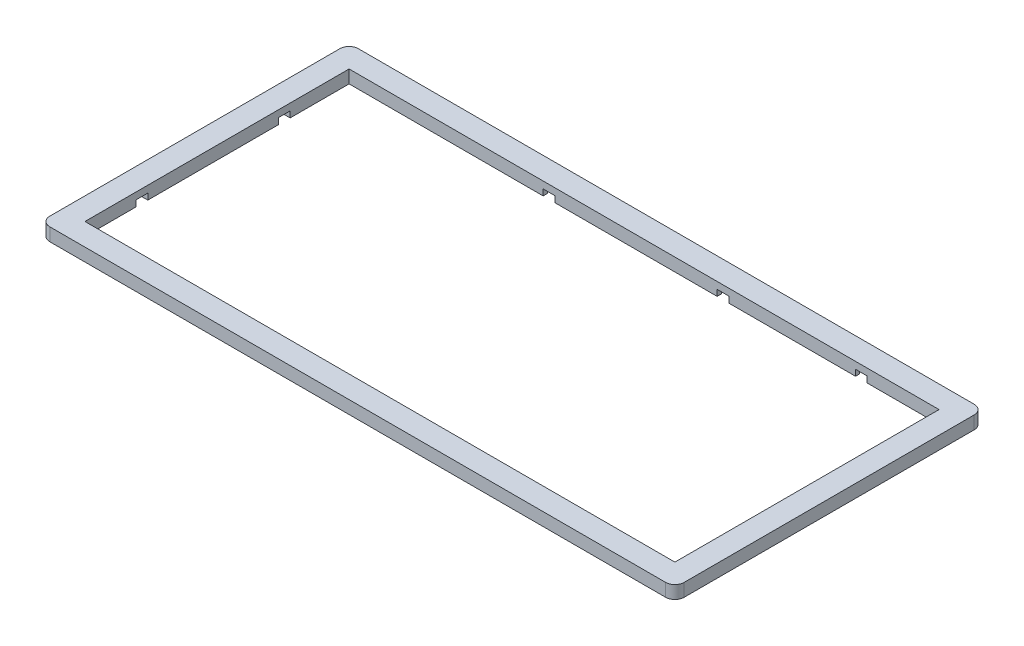
SolidWorks part; units mm, degrees
ref_plane "Front Plane" through (0, 0, 0) normal (0, 0, 1) x (1, 0, 0)
ref_plane "Top Plane" through (0, 0, 0) normal (0, 1, 0) x (1, 0, 0)
ref_plane "Right Plane" through (0, 0, 0) normal (1, 0, 0) x (0, 0, -1)
sketch "Sketch1" plane through (0, 0, 0) normal (0, 1, 0) x (1, 0, 0)
  line L0 (-142.8618, 0) -> (191.3602, 0) construction
  line L1 (0, 90.7825) -> (0, -132.7671) construction
  line L2 (-159.54, 78.7825) -> (159.54, 78.7825)
  line L3 (159.54, 78.7825) -> (159.54, -64.0925)
  line L4 (159.54, -64.0925) -> (-159.54, -64.0925)
  line L5 (-159.54, -64.0925) -> (-159.54, 78.7825)
  line L6 (-171.54, 90.7825) -> (171.54, 90.7825)
  line L7 (171.54, 90.7825) -> (171.54, -76.0925)
  line L8 (171.54, -76.0925) -> (-171.54, -76.0925)
  line L9 (-171.54, -76.0925) -> (-171.54, 90.7825)
  dimension "D1" = 319.08
  dimension "D2" = 142.875
  dimension "D3" = 12
  dimension "D4" = 12
  dimension "D5" = 12
  dimension "D6" = 12
extrude "Boss-Extrude1" add sketch "Sketch1" along normal blind 7
sketch "Sketch3" plane through (0, 0, 0) normal (0, -1, 0) x (1, 0, 0)
  line L0 (-23.85, -81.0825) -> (-48.3, -81.0825)
  line L1 (-23.85, -85.5825) -> (-23.85, -81.0825)
  line L2 (-79.05, -85.5825) -> (-23.85, -85.5825)
  line L3 (-79.05, -81.0825) -> (-79.05, -85.5825)
  line L4 (-54.6, -81.0825) -> (-79.05, -81.0825)
  line L5 (-54.6, -78.7825) -> (-54.6, -81.0825)
  line L6 (-48.3, -78.7825) -> (-54.6, -78.7825)
  line L7 (-48.3, -81.0825) -> (-48.3, -78.7825)
  line L16 (159.54, -78.7825) -> (-159.54, -78.7825) construction
  line L17 (-159.54, -78.7825) -> (-159.54, 64.0925) construction
  line L18 (145.09, -81.0825) -> (120.64, -81.0825)
  line L19 (145.09, -85.5825) -> (145.09, -81.0825)
  line L20 (89.89, -85.5825) -> (145.09, -85.5825)
  line L21 (89.89, -81.0825) -> (89.89, -85.5825)
  line L22 (114.34, -81.0825) -> (89.89, -81.0825)
  line L23 (114.34, -78.7825) -> (114.34, -81.0825)
  line L24 (120.64, -78.7825) -> (114.34, -78.7825)
  line L25 (120.64, -81.0825) -> (120.64, -78.7825)
  line L26 (70.1228, -85.5821) -> (70.1785, -81.0825)
  line L27 (14.9228, -85.5821) -> (70.1228, -85.5821)
  line L28 (14.9785, -81.0825) -> (14.9228, -85.5821)
  line L29 (39.5, -81.0825) -> (14.9785, -81.0825)
  line L30 (39.5, -78.7825) -> (39.5, -81.0825)
  line L31 (45.8, -78.7825) -> (39.5, -78.7825)
  line L32 (45.8, -81.0825) -> (45.8, -78.7825)
  line L33 (70.1785, -81.0825) -> (45.8, -81.0825)
  line L34 (-164.3573, -2.842) -> (-164.3573, -14.017) construction
  line L35 (-159.54, 36.3925) -> (-159.54, 30.0925)
  line L36 (-159.54, 36.3925) -> (-162.84, 36.3925)
  line L37 (-159.54, 30.0925) -> (-162.84, 30.0925)
  line L38 (-162.84, 36.3925) -> (-162.84, 56.3925)
  line L39 (-162.84, 30.0925) -> (-162.84, 10.0925)
  line L40 (-162.84, 56.3925) -> (-167.34, 56.3925)
  line L41 (-167.34, 56.3925) -> (-167.34, 10.0925)
  line L42 (-167.34, 10.0925) -> (-162.84, 10.0925)
  line L43 (-167.3573, -8.4295) -> (-164.3573, -8.4295) construction
  line L44 (-167.3573, 2.6105) -> (-167.3573, -19.4695) construction
  line L45 (-159.54, -40.5825) -> (-159.54, -46.8825)
  line L46 (-159.54, -40.5825) -> (-162.84, -40.5825)
  line L47 (-159.54, -46.8825) -> (-162.84, -46.8825)
  line L48 (-162.84, -40.5825) -> (-162.84, -16.1325)
  line L49 (-162.84, -16.1325) -> (-167.34, -16.1325)
  line L50 (-167.34, -16.1325) -> (-167.34, -71.3325)
  line L51 (-167.34, -71.3325) -> (-162.84, -71.3325)
  line L52 (-162.84, -71.3325) -> (-162.84, -46.8825)
  line L53 (161.84, 10.0925) -> (161.84, 30.0925)
  line L54 (-159.54, 64.0925) -> (159.54, 64.0925) construction
  line L55 (159.54, 64.0925) -> (159.54, -78.7825) construction
  line L56 (151.2867, -7.345) -> (183.3703, -7.345) construction
  line L57 (0, 81.7249) -> (0, 49.7201) construction
  line L58 (159.54, -40.5825) -> (161.84, -40.5825)
  line L59 (161.84, -40.5825) -> (161.84, -16.1325)
  line L60 (161.84, -16.1325) -> (166.34, -16.1325)
  line L61 (166.34, -16.1325) -> (166.34, -71.3325)
  line L62 (166.34, -71.3325) -> (161.84, -71.3325)
  line L63 (161.84, -71.3325) -> (161.84, -46.8825)
  line L64 (159.54, -46.8825) -> (161.84, -46.8825)
  line L65 (159.54, -40.5825) -> (159.54, -46.8825)
  line L66 (159.54, 30.0925) -> (161.84, 30.0925)
  line L68 (161.84, 56.3925) -> (166.34, 56.3925)
  line L69 (166.34, 56.3925) -> (166.34, 10.0925)
  line L70 (166.34, 10.0925) -> (161.84, 10.0925)
  line L72 (159.54, 36.3925) -> (161.84, 36.3925)
  line L73 (159.54, 30.0925) -> (159.54, 36.3925)
  line L74 (145.1081, 71.8925) -> (145.1094, 67.3925)
  line L75 (89.9081, 71.8925) -> (145.1081, 71.8925)
  line L76 (89.8706, 67.3925) -> (89.9081, 71.8925)
  line L77 (114.34, 67.3925) -> (89.8706, 67.3925)
  line L78 (114.34, 64.0925) -> (114.34, 67.3925)
  line L79 (120.64, 64.0925) -> (114.34, 64.0925)
  line L80 (120.64, 67.3925) -> (120.64, 64.0925)
  line L81 (145.1094, 67.3925) -> (120.64, 67.3925)
  line L82 (14.9512, 71.8925) -> (70.1512, 71.8925)
  line L83 (14.9783, 67.3925) -> (14.9512, 71.8925)
  line L84 (39.45, 67.3925) -> (14.9783, 67.3925)
  line L85 (39.45, 64.0925) -> (39.45, 67.3925)
  line L86 (45.75, 64.0925) -> (39.45, 64.0925)
  line L87 (45.75, 67.3925) -> (45.75, 64.0925)
  line L88 (70.1512, 67.3925) -> (45.75, 67.3925)
  line L89 (70.1512, 71.8925) -> (70.1512, 67.3925)
  line L90 (-23.81, 71.8925) -> (-23.81, 67.3925)
  line L91 (-79.01, 71.8925) -> (-23.81, 71.8925)
  line L92 (-79.01, 67.3925) -> (-79.01, 71.8925)
  line L93 (-54.54, 67.3925) -> (-79.01, 67.3925)
  line L94 (-54.54, 64.0925) -> (-54.54, 67.3925)
  line L95 (-48.2801, 64.0925) -> (-54.54, 64.0925)
  line L96 (-48.2801, 67.3925) -> (-48.2801, 64.0925)
  line L97 (-23.81, 67.3925) -> (-48.2801, 67.3925)
  line L106 (0, -68.2617) -> (0, -103.0371) construction
  line L107 (-98.744, 71.8925) -> (-98.7406, 67.3925)
  line L108 (-153.944, 71.8925) -> (-98.744, 71.8925)
  line L109 (-153.8394, 67.3925) -> (-153.944, 71.8925)
  line L110 (-129.44, 67.3925) -> (-153.8394, 67.3925)
  line L111 (-129.44, 64.0925) -> (-129.44, 67.3925)
  line L112 (-123.14, 64.0925) -> (-129.44, 64.0925)
  line L113 (-123.14, 67.3925) -> (-123.14, 64.0925)
  line L114 (-98.7406, 67.3925) -> (-123.14, 67.3925)
  line L115 (161.84, 36.3925) -> (161.84, 56.3925)
  line L116 (-159.54, 64.0925) -> (159.54, 64.0925) construction
  point P51 (-164.3573, -8.4295)
  dimension "D4" = 30.1
  dimension "D5" = 6.3
  dimension "D6" = 4.5
  dimension "D7" = 55.2
  dimension "D8" = 6.3
  dimension "D9" = 6.3
  dimension "D10" = 2.3
  dimension "D11" = 55.2
  dimension "D12" = 39.5
  dimension "D13" = 6.3
  dimension "D14" = 4.5
  dimension "D15" = 55.2
  dimension "D16" = 6.3
  dimension "D17" = 22.08
  dimension "D18" = 3
  dimension "D19" = 6.3
  dimension "D20" = 55.2
  dimension "D21" = 4.5
  dimension "D22" = 31.9
  dimension "D23" = 27.7
  dimension "D24" = 3.3
  dimension "D25" = 3.3
  dimension "D26" = 46.3
  dimension "D27" = 4.5
  dimension "D28" = 6.2599
  dimension "D29" = 68.6
  dimension "D30" = 39.45
  dimension "D31" = 55.2
  dimension "D32" = 6.3
  dimension "D33" = 38.9
  dimension "D34" = 6.3
  dimension "D35" = 27.7
  dimension "D36" = 31.9
  dimension "D37" = 55.2
  dimension "D38" = 38.9
  dimension "D39" = 3.3
  dimension "D40" = 4.5
  dimension "D41" = 55.2
  dimension "D42" = 48.3
  dimension "D43" = 6.3
  dimension "D44" = 2.3
  dimension "D45" = 46.3
  dimension "D46" = 6.3
  dimension "D47" = 2.3
  dimension "D48" = 4.5
  dimension "D49" = 3.3
  dimension "D50" = 4.5
  dimension "D51" = 3.3
  dimension "D52" = 4.5
  dimension "D53" = 55.2
  dimension "D54" = 4.5
  dimension "D55" = 2.3
  dimension "D56" = 4.5
  dimension "D57" = 2.3
  dimension "D58" = 3.3
  dimension "D59" = 4.5
  dimension "D60" = 55.2
fillet "Fillet1" radius 5 1 edges at (171.54, 3.5, 76.0925)
fillet "Fillet2" radius 5 1 edges at (-171.54, 3.5, -90.7825)
fillet "Fillet3" radius 5 1 edges at (-171.54, 3.5, 76.0925)
extrude "Cut-Extrude2" cut sketch "Sketch3" against normal blind 3.3
fillet "Fillet5" radius 5 1 edges at (171.54, 3.5, -90.7825)
